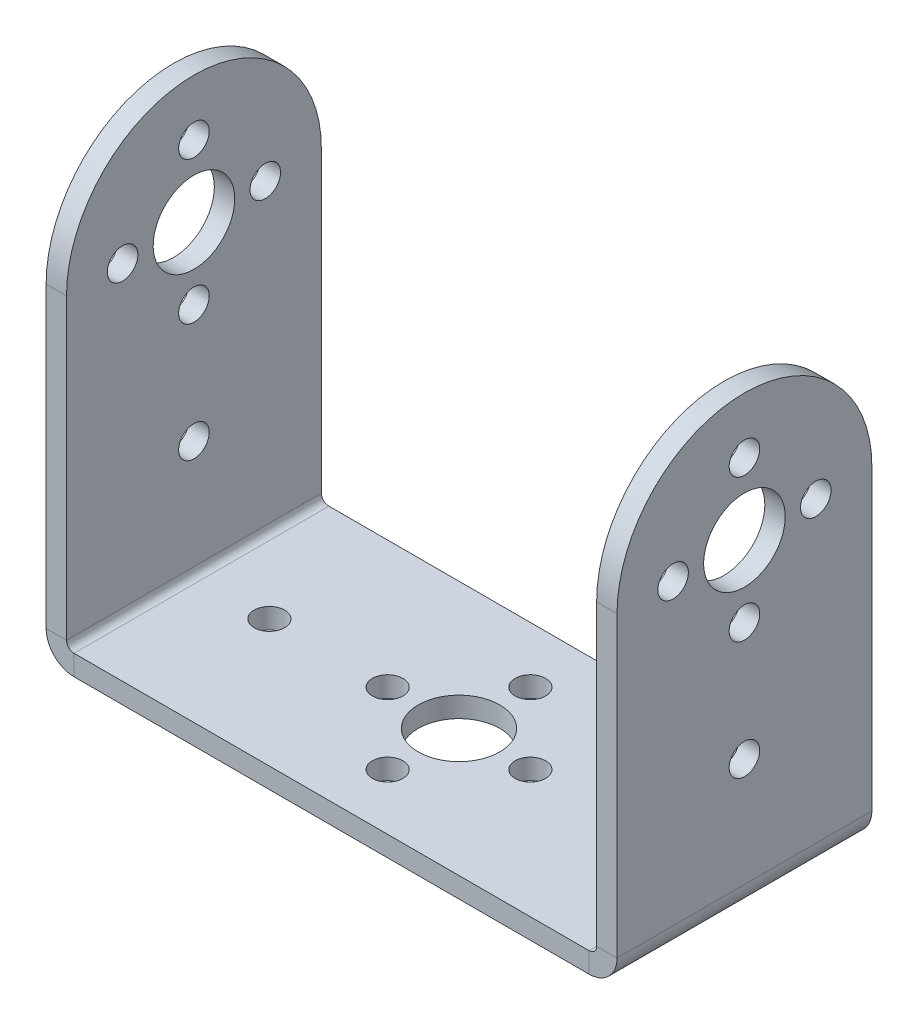
SolidWorks part; units mm, degrees
note: The reader was unsure of these and kept them because the rebuilt part matched: flange length of "边线-法兰1".
ref_plane "前视基准面" through (0, 0, 0) normal (0, 0, 1) x (1, 0, 0)
ref_plane "上视基准面" through (0, 0, 0) normal (0, 1, 0) x (1, 0, 0)
ref_plane "右视基准面" through (0, 0, 0) normal (1, 0, 0) x (0, 0, -1)
sketch "草图1" plane through (0, 0, 0) normal (0, 1, 0) x (1, 0, 0)
  line L1 (-26, 12.5) -> (26, 12.5)
  line L2 (-26, 12.5) -> (-26, -12.5)
  line L3 (-26, -12.5) -> (26, -12.5)
  line L4 (26, 12.5) -> (26, -12.5)
  line L5 (-26, 12.5) -> (26, -12.5) construction
  line L6 (-26, -12.5) -> (26, 12.5) construction
  point P0 (0, 0)
  point P14 (0, 0)
  point P17 (0, 0)
  point P20 (0, 0)
  point P23 (0, 0)
  dimension "D1" = 52
  dimension "D2" = 25
  dimension "D6" = 4
base flange "基体-法兰1" sketch "草图1" thickness 2 reverse thickness direction no parameters "D1"=0.7366
edge flange "边线-法兰1" sketch "草图4" flange angle 90 flange length 30 flange position material outside bend radius 0.7366 thickness 2 relief rectangular parameters "D6"=10
sketch "草图4" plane through (26, 0, 0) normal (1, 0, 0) x (0, 0, -1)
  line L0 (-12.5, 0) -> (12.5, 0) construction
  line L1 (-12.5, 0) -> (12.5, 0)
  line L2 (-12.5, 0) -> (-12.5, 30)
  line L4 (12.5, 30) -> (12.5, 0)
  arc A7 (-12.5, 30) -> (12.5, 30) centre (0, 30) cw
  point P21 (0, 30)
  dimension "D1" = 12.5
  dimension "D5" = 30
bend "边线折弯1" bend radius 0.7366 bend angle 90 parameters "D5"=1
mirror "镜向1" about plane through (0, 0, 0) normal (1, 0, 0) of "边线-法兰1"
bend "镜向折弯1" bend radius 0.7366 bend angle 90 parameters "D5"=2
hole_wizard "Ø3.0 (3) 直径孔1" positions "草图8" profile "草图9" hole size "Ø3.0" standard "GB"
sketch "草图8" plane through (0, -2, 0) normal (0, -1, 0) x (-1, 0, 0)
  circle A0 centre (0, 0) radius 7 construction
  point P0 (0, -7)
  point P2 (0, 7)
  point P4 (-7, 0)
  point P6 (7, 0)
  point P8 (18.6, 0)
  point P10 (-18.6, 0)
  point P17 (0, 0)
  point P18 (0, 0)
  point P19 (0, 0)
  point P20 (0, 0)
  point P21 (0, 0)
  point P22 (0, 0)
  point P23 (0, 0)
  dimension "D1" = 14
  dimension "D2" = 18.6
  dimension "D3" = 18.6
sketch "草图9" plane through (0, -2, 7) normal (1, 0, 0) x (0, 0, -1)
  line L0 (0, 0) -> (0, 2.9003)
  line L1 (0, 2.9003) -> (1.5, 1.999)
  line L2 (1.5, 1.999) -> (1.5, 0)
  line L5 (1.5, 0) -> (0, 0)
  line L10 (0, 2.9003) -> (-1.5, 1.999) construction
  line L11 (0, -6.35) -> (0, 107.95) construction
  dimension "孔直径" = 3
  dimension "孔深度" = 1.999
  dimension "导头角度" = 118
hole_wizard "Ø8.0 (8) 直径孔1" positions "草图10" profile "草图11" hole size "Ø8.0" standard "GB"
sketch "草图10" plane through (0, -2, 0) normal (0, -1, 0) x (-1, 0, 0)
  point P2 (0, 0)
  point P6 (0, 0)
sketch "草图11" plane through (0, -2, 0) normal (1, 0, 0) x (0, 0, -1)
  line L0 (0, 0) -> (0, 4.4024)
  line L1 (0, 4.4024) -> (4, 1.999)
  line L2 (4, 1.999) -> (4, 0)
  line L5 (4, 0) -> (0, 0)
  line L10 (0, 4.4024) -> (-4, 1.999) construction
  line L11 (0, -6.35) -> (0, 107.95) construction
  dimension "孔直径" = 8
  dimension "孔深度" = 1.999
  dimension "导头角度" = 118
hole_wizard "Ø3.0 (3) 直径孔2" positions "草图12" profile "草图13" hole size "Ø3.0" standard "GB" end condition through all
sketch "草图12" plane through (28, 0, 0) normal (1, 0, 0) x (0, 0, -1)
  circle A0 centre (0, 30) radius 7 construction
  point P0 (0, 11.4)
  point P4 (0, 37)
  point P6 (7, 30)
  point P8 (-7, 30)
  point P10 (0, 23)
  point P16 (0, 0)
  point P17 (0, 0)
  point P18 (0, 0)
  point P19 (0, 0)
  point P20 (0, 0)
  point P21 (0, 0)
  point P22 (0, 0)
  point P24 (0, 0)
  dimension "D1" = 14
  dimension "D2" = 18.6
  dimension "D3" = 30
sketch "草图13" plane through (28, 11.4, 0) normal (0, 1, 0) x (0, 0, -1)
  line L0 (0, 0) -> (0, 56)
  line L1 (0, 56) -> (1.5, 56)
  line L2 (1.5, 56) -> (1.5, 0)
  line L5 (1.5, 0) -> (0, 0)
  line L11 (0, -6.35) -> (0, 107.95) construction
  dimension "通孔孔直径" = 3
  dimension "通孔孔深度" = 56
hole_wizard "Ø8.0 (8) 直径孔2" positions "草图14" profile "草图15" hole size "Ø8.0" standard "GB" end condition through all
sketch "草图14" plane through (28, 0, 0) normal (1, 0, 0) x (0, 0, -1)
  point P0 (0, 30)
  point P4 (0, 0)
  dimension "D1" = 30
sketch "草图15" plane through (28, 30, 0) normal (0, 1, 0) x (0, 0, -1)
  line L0 (0, 0) -> (0, 56)
  line L1 (0, 56) -> (4, 56)
  line L2 (4, 56) -> (4, 0)
  line L5 (4, 0) -> (0, 0)
  line L11 (0, -6.35) -> (0, 107.95) construction
  dimension "通孔孔直径" = 8
  dimension "通孔孔深度" = 56
sketch "折弯-线1" [suppressed] plane through (0, 0, 0) normal (0, 1, 0) x (1, 0, 0)
sketch "边界框1" [suppressed] plane through (0, 0, 0) normal (0, 1, 0) x (1, 0, 0)
sheet metal parameters "钣金1" thickness 2 parameters "D1"=0.7366
flat pattern "平板型式1" [suppressed]
sketch "折弯-线2" plane through (0, 0, 0) normal (0, 1, 0) x (1, 0, 0)
sketch3d "边界框2" [suppressed]
  line L0 (26, -12.5, 0) -> (-26, -12.5, 0) construction
  line L1 (26, 12.5, 0) -> (-26, 12.5, 0) construction
  line L2 (26, -12.5, 0) -> (26, 12.5, 0) construction
  line L3 (-26, -12.5, 0) -> (-26, 12.5, 0) construction
sheet metal parameters "钣金5" thickness 2 parameters "D1"=0.7366
flat pattern "平板型式1"
sketch "折弯-线2" plane through (0, 0, 0) normal (0, 1, 0) x (1, 0, 0)
  line L0 (26.6273, -12.5) -> (26.6273, 12.5) construction
  line L1 (26.6273, -12.5) -> (26.6273, 12.5) construction
sketch3d "边界框2" [suppressed]
  line L0 (69.7546, -12.5, 0) -> (-26, -12.5, 0) construction
  line L1 (69.7546, 12.5, 0) -> (-26, 12.5, 0) construction
  line L2 (69.7546, -12.5, 0) -> (69.7546, 12.5, 0) construction
  line L3 (-26, -12.5, 0) -> (-26, 12.5, 0) construction
bend of the flat pattern "展开-<边线折弯1>1"
sheet metal parameters "钣金6" thickness 2 parameters "D1"=0.7366
flat pattern "平板型式1"
sketch "折弯-线2" plane through (0, 0, 0) normal (0, 1, 0) x (1, 0, 0)
  line L0 (26.6273, -12.5) -> (26.6273, 12.5) construction
  line L1 (26.6273, -12.5) -> (26.6273, 12.5) construction
  line L2 (-26.6273, 12.5) -> (-26.6273, -12.5) construction
  line L3 (-26.6273, 12.5) -> (-26.6273, -12.5) construction
sketch3d "边界框2" [suppressed]
  line L0 (69.7546, -12.5, 0) -> (-69.7546, -12.5, 0) construction
  line L1 (69.7546, 12.5, 0) -> (-69.7546, 12.5, 0) construction
  line L2 (69.7546, -12.5, 0) -> (69.7546, 12.5, 0) construction
  line L3 (-69.7546, -12.5, 0) -> (-69.7546, 12.5, 0) construction
bend of the flat pattern "展开-<边线折弯1>1"
bend of the flat pattern "展开-<镜向折弯1>1"
sheet metal parameters "钣金7" thickness 2 parameters "D1"=0.7366
flat pattern "平板型式1"
sketch "折弯-线2" plane through (0, 0, 0) normal (0, 1, 0) x (1, 0, 0)
  line L0 (26.6273, -12.5) -> (26.6273, 12.5) construction
  line L1 (26.6273, -12.5) -> (26.6273, 12.5) construction
  line L2 (-26.6273, 12.5) -> (-26.6273, -12.5) construction
  line L3 (-26.6273, 12.5) -> (-26.6273, -12.5) construction
sketch3d "边界框2" [suppressed]
  line L0 (69.7546, -12.5, 0) -> (-69.7546, -12.5, 0) construction
  line L1 (69.7546, 12.5, 0) -> (-69.7546, 12.5, 0) construction
  line L2 (69.7546, -12.5, 0) -> (69.7546, 12.5, 0) construction
  line L3 (-69.7546, -12.5, 0) -> (-69.7546, 12.5, 0) construction
bend of the flat pattern "展开-<边线折弯1>1"
bend of the flat pattern "展开-<镜向折弯1>1"
sheet metal parameters "钣金8" thickness 2 parameters "D1"=0.7366
flat pattern "平板型式1"
sketch "折弯-线2" plane through (0, 0, 0) normal (0, 1, 0) x (1, 0, 0)
  line L0 (26.6273, -12.5) -> (26.6273, 12.5) construction
  line L1 (26.6273, -12.5) -> (26.6273, 12.5) construction
  line L2 (-26.6273, 12.5) -> (-26.6273, -12.5) construction
  line L3 (-26.6273, 12.5) -> (-26.6273, -12.5) construction
sketch3d "边界框2" [suppressed]
  line L0 (69.7546, -12.5, 0) -> (-69.7546, -12.5, 0) construction
  line L1 (69.7546, 12.5, 0) -> (-69.7546, 12.5, 0) construction
  line L2 (69.7546, -12.5, 0) -> (69.7546, 12.5, 0) construction
  line L3 (-69.7546, -12.5, 0) -> (-69.7546, 12.5, 0) construction
bend of the flat pattern "展开-<边线折弯1>1"
bend of the flat pattern "展开-<镜向折弯1>1"
sheet metal parameters "钣金9" thickness 2 parameters "D1"=0.7366
flat pattern "平板型式1"
sketch "折弯-线2" plane through (0, 0, 0) normal (0, 1, 0) x (1, 0, 0)
  line L0 (26.6273, -12.5) -> (26.6273, 12.5) construction
  line L1 (26.6273, -12.5) -> (26.6273, 12.5) construction
  line L2 (-26.6273, 12.5) -> (-26.6273, -12.5) construction
  line L3 (-26.6273, 12.5) -> (-26.6273, -12.5) construction
sketch3d "边界框2" [suppressed]
  line L0 (69.7546, -12.5, 0) -> (-69.7546, -12.5, 0) construction
  line L1 (69.7546, 12.5, 0) -> (-69.7546, 12.5, 0) construction
  line L2 (69.7546, -12.5, 0) -> (69.7546, 12.5, 0) construction
  line L3 (-69.7546, -12.5, 0) -> (-69.7546, 12.5, 0) construction
bend of the flat pattern "展开-<边线折弯1>1"
bend of the flat pattern "展开-<镜向折弯1>1"
sheet metal parameters "钣金10" thickness 2 parameters "D1"=0.7366
flat pattern "平板型式1"
sketch "折弯-线2" plane through (0, 0, 0) normal (0, 1, 0) x (1, 0, 0)
  line L0 (26.6273, -12.5) -> (26.6273, 12.5) construction
  line L1 (26.6273, -12.5) -> (26.6273, 12.5) construction
  line L2 (-26.6273, 12.5) -> (-26.6273, -12.5) construction
  line L3 (-26.6273, 12.5) -> (-26.6273, -12.5) construction
sketch3d "边界框2" [suppressed]
  line L0 (69.7546, -12.5, 0) -> (-69.7546, -12.5, 0) construction
  line L1 (69.7546, 12.5, 0) -> (-69.7546, 12.5, 0) construction
  line L2 (69.7546, -12.5, 0) -> (69.7546, 12.5, 0) construction
  line L3 (-69.7546, -12.5, 0) -> (-69.7546, 12.5, 0) construction
bend of the flat pattern "展开-<边线折弯1>1"
bend of the flat pattern "展开-<镜向折弯1>1"
